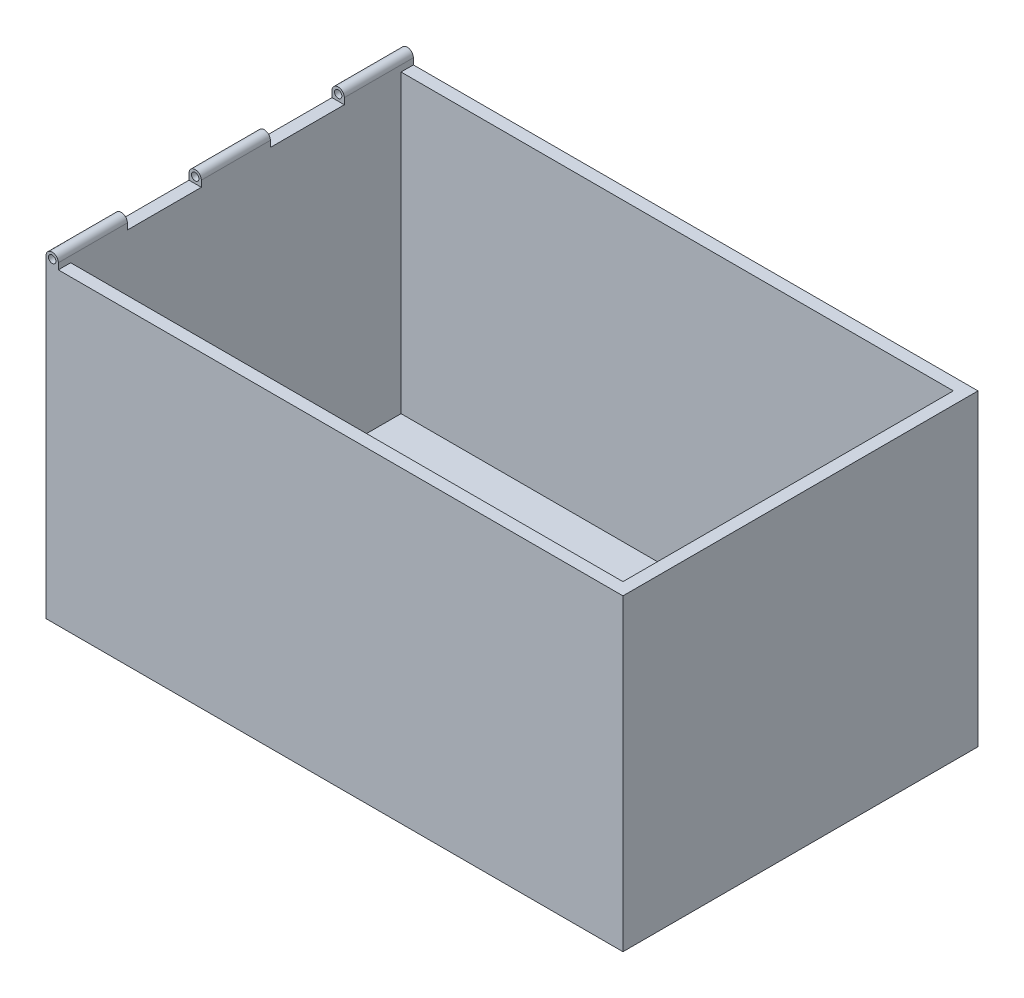
SolidWorks part; units mm, degrees
ref_plane "Front Plane" through (0, 0, 0) normal (0, 0, 1) x (1, 0, 0)
ref_plane "Top Plane" through (0, 0, 0) normal (0, 1, 0) x (1, 0, 0)
ref_plane "Right Plane" through (0, 0, 0) normal (1, 0, 0) x (0, 0, -1)
sketch "Sketch1" plane through (0, 0, 0) normal (0, 1, 0) x (1, 0, 0)
  line L1 (-58.5, 36) -> (58.5, 36)
  line L2 (-58.5, 36) -> (-58.5, -36)
  line L3 (-58.5, -36) -> (58.5, -36)
  line L4 (58.5, 36) -> (58.5, -36)
  point P4 (0, 36)
  point P6 (-58.5, 0)
  dimension "D1" = 117
  dimension "D2" = 72
extrude "Boss-Extrude1" add sketch "Sketch1" against normal blind 2.5
sketch "Sketch2" plane through (0, 0, 0) normal (0, 1, 0) x (1, 0, 0)
  line L1 (-58.5, 36) -> (58.5, 36)
  line L2 (-58.5, 36) -> (-58.5, -36)
  line L3 (-58.5, -36) -> (58.5, -36)
  line L4 (58.5, 36) -> (58.5, -36)
  line L5 (-56, 33.5) -> (56, 33.5)
  line L6 (-56, 33.5) -> (-56, -33.5)
  line L7 (-56, -33.5) -> (56, -33.5)
  line L8 (56, 33.5) -> (56, -33.5)
  dimension "D1" = 2.5
  dimension "D2" = 2.5
  dimension "D3" = 2.5
  dimension "D4" = 2.5
extrude "Boss-Extrude2" add sketch "Sketch2" along normal blind 60
sketch "Sketch3" plane through (0, 0, 0) normal (0, 0, 1) x (1, 0, 0)
  line L0 (-58.5, 61.25) -> (-58.5, 60)
  line L1 (-58.5, 60) -> (-56, 60) construction
  line L2 (-58.5, 60) -> (58.5, 60) construction
  line L3 (-58.5, 60) -> (-56, 60)
  line L6 (-56, 60) -> (-56, 61.25)
  arc A0 (-58.5, 61.25) -> (-56, 61.25) centre (-57.25, 61.25) cw
  circle A1 centre (-57.25, 61.25) radius 0.75
  point P9 (-57.25, 62.5)
  dimension "D1" = 2.5
  dimension "D2" = 1.5
  dimension "D3" = 2.5
extrude "Boss-Extrude3" add sketch "Sketch3" against normal mid plane 72
sketch "Sketch4" plane through (0, 0, 0) normal (1, 0, 0) x (0, 0, -1)
  line L0 (36, 62.5) -> (-36, 62.5) construction
  line L1 (-22, 62.5) -> (-7, 62.5)
  line L2 (-22, 62.5) -> (-22, 60)
  line L3 (-22, 60) -> (-7, 60)
  line L4 (-7, 62.5) -> (-7, 60)
  line L5 (-36, 60) -> (36, 60) construction
  line L6 (-36, -2.5) -> (-36, 60) construction
  line L7 (7, 62.5) -> (22, 62.5)
  line L8 (7, 62.5) -> (7, 60)
  line L9 (7, 60) -> (22, 60)
  line L10 (22, 62.5) -> (22, 60)
  line L11 (36, -2.5) -> (36, 60) construction
  dimension "D1" = 14
  dimension "D2" = 14
  dimension "D3" = 14
extrude "Cut-Extrude1" cut sketch "Sketch4" against normal through all both and the other way through all
sketch "Sketch5" plane through (0, 0, 0) normal (0, 1, 0) x (1, 0, 0)
  line L0 (-43.615, 25.5) -> (-17.1257, 25.5) construction
  line L1 (56, 33.5) -> (-56, 33.5) construction
  dimension "D1" = 8
sketch "Sketch6" plane through (0, 0, 0) normal (0, 1, 0) x (1, 0, 0)
  line L0 (13.1831, 25.5) -> (13.1831, 14.2303) construction
  line L1 (-43.615, 25.5) -> (-17.1257, 25.5) construction
equation "\"wall\"=2.5"
equation "\"D1@Boss-Extrude1\"=\"wall\""
equation "\"D1@Sketch2\"=\"wall\""
equation "\"D2@Sketch2\"=\"wall\""
equation "\"D3@Sketch2\"=\"wall\""
equation "\"D4@Sketch2\"=\"wall\""
equation "\"box_width\"=112"
equation "\"D1@Sketch1\"=\"wall\"*2+\"box_width\""
equation "\"box_length\"= 67"
equation "\"D2@Sketch1\"=\"wall\"*2+\"box_length\""
equation "\"D1@Sketch3\"=\"wall\""
equation "\"axis_hole\"= 1.5"
equation "\"D2@Sketch3\"=\"axis_hole\""
equation "\"D3@Sketch3\"=\"wall\""
equation "\"D1@Boss-Extrude3\"=\"box_length\"+\"wall\"*2"
